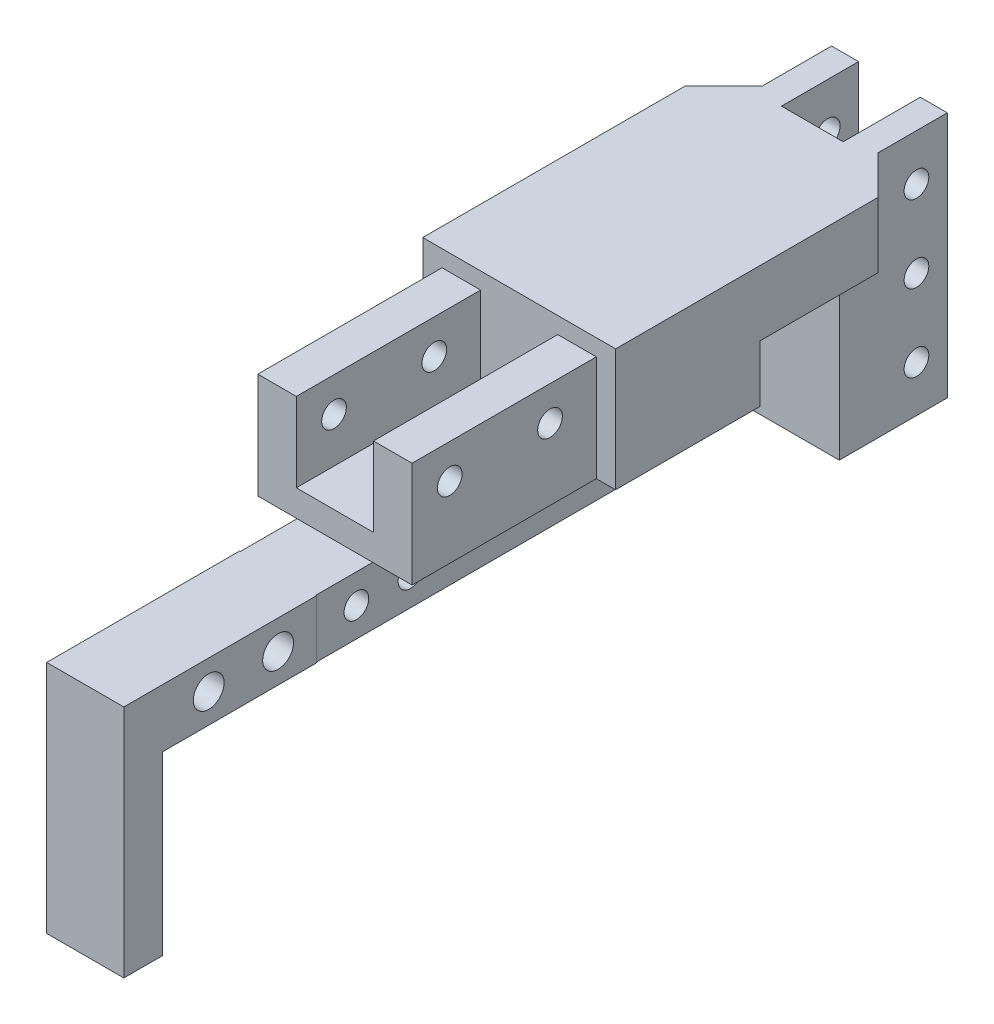
SolidWorks part; units mm, degrees
ref_plane "前视基准面" through (0, 0, 0) normal (0, 0, 1) x (1, 0, 0)
ref_plane "上视基准面" through (0, 0, 0) normal (0, 1, 0) x (1, 0, 0)
ref_plane "右视基准面" through (0, 0, 0) normal (1, 0, 0) x (0, 0, -1)
sketch "草图2" plane through (0, 0, 0) normal (1, 0, 0) x (0, 0, -1)
  line L0 (7, 0) -> (32.5, 0) construction
  line L2 (44.75, 3.775) -> (-5.25, 3.775)
  line L3 (44.75, 3.775) -> (44.75, -3.775)
  line L4 (44.75, -3.775) -> (-5.25, -3.775)
  line L5 (-5.25, 3.775) -> (-5.25, -3.775)
  line L6 (44.75, 3.775) -> (-5.25, -3.775) construction
  line L7 (44.75, -3.775) -> (-5.25, 3.775) construction
  circle A0 centre (0, 0) radius 1.6
  circle A1 centre (7, 0) radius 1.6
  circle A2 centre (32.5, 0) radius 1.6
  circle A3 centre (39.5, 0) radius 1.6
  point P9 (19.75, 0)
extrude "凸台-拉伸1" add sketch "草图2" along normal mid plane 9.8
sketch "草图3" plane through (0, 0, 0) normal (1, 0, 0) x (0, 0, -1)
  line L0 (7, 13) -> (20, 13) construction
  line L1 (2.1144, 3.775) -> (2.1144, 17.4551)
  line L2 (44.75, 3.775) -> (-5.25, 3.775) construction
  line L3 (2.1144, 17.4551) -> (26, 17.4551)
  line L4 (26, 17.4551) -> (26, 3.775)
  line L5 (26, 3.775) -> (2.1144, 3.775)
  circle A0 centre (7, 13) radius 1.6
  circle A1 centre (20, 13) radius 1.6
  point P0 (7, 0)
  point P6 (13.5, 13)
  dimension "D1" = 13
  dimension "D3" = 3.2
  dimension "D4" = 3.2
  dimension "D2" = 6
extrude "凸台-拉伸2" add sketch "草图3" along normal mid plane 20
sketch "草图4" plane through (0, 0, -2.1144) normal (0, 0, 1) x (1, 0, 0)
  line L0 (10, 17.4551) -> (-10, 17.4551) construction
  line L1 (5, 7.1905) -> (-5, 7.1905)
  line L2 (5, 7.1905) -> (5, 17.4551)
  line L3 (5, 17.4551) -> (-5, 17.4551)
  line L4 (-5, 7.1905) -> (-5, 17.4551)
  line L5 (5, 7.1905) -> (-5, 17.4551) construction
  line L6 (5, 17.4551) -> (-5, 7.1905) construction
  point P0 (0, 12.3228)
extrude "切除-拉伸1" cut sketch "草图4" against normal through all
sketch "草图6" plane through (0, 0, 0) normal (1, 0, 0) x (0, 0, -1)
  line L0 (70, 3.6) -> (70, 13.6) construction
  line L2 (74, -12.4) -> (60, -12.4)
  line L3 (74, -12.4) -> (74, 19.6)
  line L4 (74, 19.6) -> (60, 19.6)
  line L5 (60, -12.4) -> (60, 19.6)
  line L6 (74, -12.4) -> (60, 19.6) construction
  line L7 (74, 19.6) -> (60, -12.4) construction
  circle A0 centre (70, 3.6) radius 1.6
  circle A1 centre (70, 13.6) radius 1.6
  circle A2 centre (70, -6.4) radius 1.6
  point P4 (70, 8.6)
  point P9 (67, 3.6)
  dimension "D1" = 60
  dimension "D6" = 10
  dimension "D2" = 3.6
  dimension "D3" = 10
  dimension "D4" = 4
  dimension "D5" = 14
  dimension "D7" = 6
  dimension "D8" = 6
extrude "凸台-拉伸4" add sketch "草图6" along normal mid plane 15 separate body
sketch "草图7" plane through (0, 0, -74) normal (0, 0, 1) x (1, 0, 0)
  line L0 (7.5, 19.6) -> (-7.5, 19.6) construction
  line L1 (-4, 19.6) -> (4, 19.6)
  line L2 (-4, 19.6) -> (-4, -12.4)
  line L3 (-4, -12.4) -> (4, -12.4)
  line L4 (4, 19.6) -> (4, -12.4)
  line L5 (7.5, -12.4) -> (-7.5, -12.4) construction
extrude "切除-拉伸2" cut sketch "草图7" along normal blind 10
sketch "草图8" plane through (0, 0, 0) normal (1, 0, 0) x (0, 0, -1)
  line L0 (26, 3.775) -> (26, 17.4551) construction
  line L1 (60, 19.6) -> (26, 19.6)
  line L2 (60, 19.6) -> (60, 11.1399)
  line L3 (60, 11.1399) -> (44.75, 11.1399)
  line L4 (26, 19.6) -> (26, 11.1399)
  line L7 (26, 11.1399) -> (26, 3.775)
  line L8 (26, 3.775) -> (44.75, 3.775)
  line L9 (44.75, 11.1399) -> (44.75, 3.775)
extrude "凸台-拉伸5" add sketch "草图8" along normal mid plane 25
chamfer "倒角1" distance 5 angle 45 2 edges at (-7.5, 15.37, -60) (7.5, 15.37, -60)
sketch "草图10" plane through (0, 0, 0) normal (1, 0, 0) x (0, 0, -1)
  line L0 (-5.25, 3.775) -> (-5.25, -3.775)
  line L1 (-5.25, -3.775) -> (-25.25, -3.775)
  line L2 (-25.25, -3.775) -> (-25.25, -26.6539)
  line L3 (-30.25, -26.6539) -> (-30.25, 3.775)
  line L4 (-30.25, 3.775) -> (-5.25, 3.775)
  line L5 (-30.25, -26.6539) -> (-25.25, -26.6539)
  circle A0 centre (-10.25, 0) radius 2
  circle A1 centre (-19.25, 0) radius 2
  dimension "D3" = 4
  dimension "D4" = 4
  dimension "D1" = 20
  dimension "D2" = 5
  dimension "D5" = 9
  dimension "D6" = 5
extrude "凸台-拉伸6" add sketch "草图10" along normal mid plane 10
